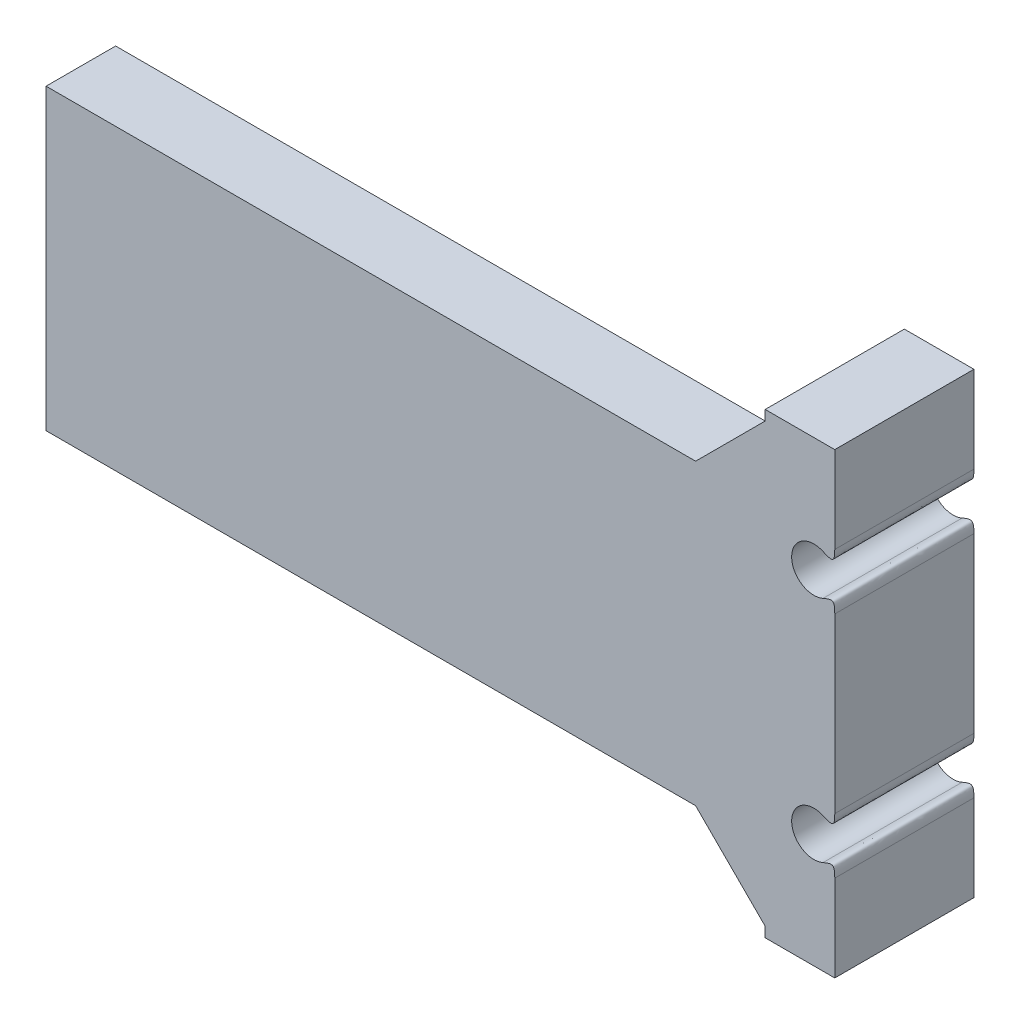
SolidWorks part; units mm, degrees
ref_plane "Alzado" through (0, 0, 0) normal (0, 0, 1) x (1, 0, 0)
ref_plane "Planta" through (0, 0, 0) normal (0, 1, 0) x (1, 0, 0)
ref_plane "Vista lateral" through (0, 0, 0) normal (1, 0, 0) x (0, 0, -1)
sketch "Croquis1" plane through (0, 0, 0) normal (0, 0, 1) x (1, 0, 0)
  line L5 (-5, -7.2848) -> (-10, -7.2848)
  line L6 (-10, -7.2848) -> (-10, -1.5636)
  line L7 (-10, 25.6) -> (-5, 25.6)
  line L8 (-10, 19.8788) -> (-61.678, 19.8788)
  line L9 (-61.678, 19.8788) -> (-61.678, -1.5636)
  line L10 (-61.678, -1.5636) -> (-10, -1.5636)
  line L11 (-10, 19.8788) -> (-10, 25.6)
  line L16 (-5, 25.6) -> (-5, 17.9356)
  line L17 (-5, 0.3796) -> (-5, -7.2848)
  line L18 (-5, 16.822) -> (-5, 1.4932)
  arc A0 (-5, 17.9356) -> (-5, 16.822) centre (-6.5, 17.3788) ccw
  arc A1 (-5, 1.4932) -> (-5, 0.3796) centre (-6.5, 0.9364) ccw
extrude "Saliente-Extruir1" add sketch "Croquis1" against normal blind 10
chamfer "Chaflán1" distance 5 angle 45 2 edges at (-10, -1.5636, -5) (-10, 19.8788, -5)
sketch "Croquis2" plane through (-7.1021, -7.2848, 0) normal (0, 1, 0) x (0, 0, -1)
  line L5 (5, 7.8979) -> (5, 54.5759)
  line L6 (5, 54.5759) -> (10, 54.5759)
  line L11 (5, 7.8979) -> (10, 2.8979)
  line L12 (10, 2.8979) -> (10, 54.5759)
  line L13 (0, -1.2259) -> (5, 7.8979) construction
  line L14 (10, 7.8979) -> (0, 7.8979) construction
  line L15 (10, 54.5759) -> (0, 54.5759) construction
extrude "Cortar-Extruir1" cut sketch "Croquis2" along normal blind 38
fillet "Redondeo1" radius 0.6 4 edges at (-5, 17.9356, -5) (-5, 16.822, -5) (-5, 0.3796, -5) (-5, 1.4932, -5) conic rho 0.65
